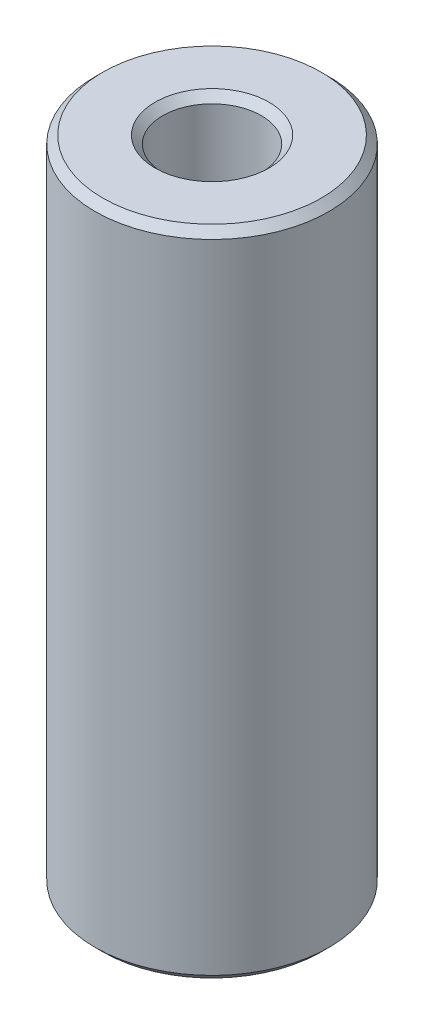
SolidWorks part; units mm, degrees
ref_plane "Front Plane" through (0, 0, 0) normal (0, 0, 1) x (1, 0, 0)
ref_plane "Top Plane" through (0, 0, 0) normal (0, 1, 0) x (1, 0, 0)
ref_plane "Right Plane" through (0, 0, 0) normal (1, 0, 0) x (0, 0, -1)
sketch "Sketch1" plane through (0, 0, 0) normal (0, 1, 0) x (1, 0, 0)
  circle A0 centre (0, 0) radius 30
  dimension "SLEEVE_OD" = 60
extrude "Boss-Extrude1" add sketch "Sketch1" along normal blind 167.5178
sketch "Sketch2" plane through (0, 0, 0) normal (0, 1, 0) x (1, 0, 0)
  circle A0 centre (0, 0) radius 12.6534
  dimension "BORE_D" = 25.3067
extrude "Cut-Extrude1" cut sketch "Sketch2" along normal through all
chamfer "Chamfer1" distance 1.9872 angle 45 4 edges at (0, 167.5178, 12.6534) (0, 0, 12.6534) (0, 0, 30) (0, 167.5178, 30)
